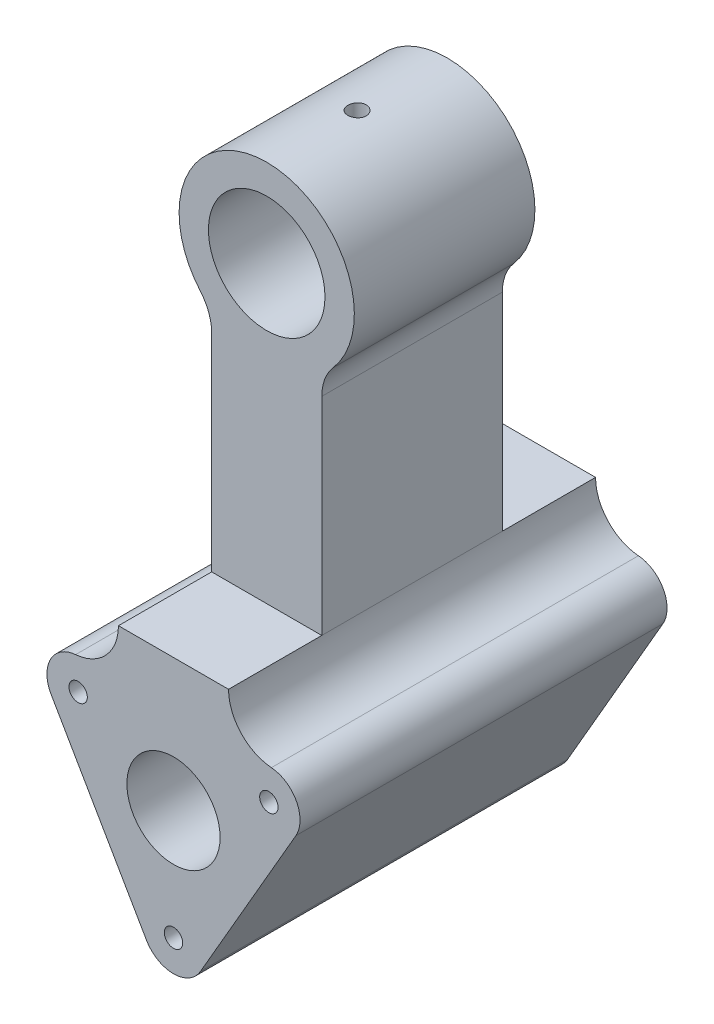
SolidWorks part; units mm, degrees
material "6061-T6 (SS)"
ref_plane "Front Plane" through (0, 0, 0) normal (0, 0, 1) x (1, 0, 0)
ref_plane "Top Plane" through (0, 0, 0) normal (0, 1, 0) x (1, 0, 0)
ref_plane "Right Plane" through (0, 0, 0) normal (1, 0, 0) x (0, 0, -1)
sketch "Sketch1" plane through (0, 0, 0) normal (0, 0, 1) x (1, 0, 0)
  line L22 (-16.671, -52.8382) -> (-3.6806, -75.3382)
  line L23 (3.6806, -75.3382) -> (16.671, -52.8382)
  line L24 (-7.5, -11.9419) -> (-7.5, -40.1481)
  line L25 (7.5, -11.9419) -> (7.5, -40.1481)
  line L26 (-7.5, -40.1481) -> (7.5, -40.1481)
  line L27 (-12.9904, -50.7132) -> (0, -58.2132) construction
  line L28 (0, -58.2132) -> (12.9904, -50.7132) construction
  line L29 (0, -73.2132) -> (0, -58.2132) construction
  circle A0 centre (0, 0) radius 7.9375
  arc A26 (-9.0408, -7.7953) -> (9.0408, -7.7953) centre (0, 0) cw
  arc A30 (-13.335, -46.4772) -> (-16.671, -52.8382) centre (-12.9904, -50.7132) ccw
  arc A31 (-3.6806, -75.3382) -> (3.6806, -75.3382) centre (0, -73.2132) ccw
  arc A32 (16.671, -52.8382) -> (13.335, -46.4772) centre (12.9904, -50.7132) ccw
  circle A33 centre (0, -73.2132) radius 1.65 construction
  circle A34 centre (12.9904, -50.7132) radius 1.65 construction
  circle A35 centre (-12.9904, -50.7132) radius 1.25
  circle A36 centre (12.9904, -50.7132) radius 1.25
  circle A37 centre (0, -73.2132) radius 1.25
  arc A38 (-7.5, -40.1481) -> (-13.335, -46.4772) centre (-13.85, -40.1481) cw
  arc A39 (7.5, -40.1481) -> (13.335, -46.4772) centre (13.85, -40.1481) ccw
  arc A40 (9.0408, -7.7953) -> (7.5, -11.9419) centre (13.85, -11.9419) ccw
  arc A41 (-9.0408, -7.7953) -> (-7.5, -11.9419) centre (-13.85, -11.9419) cw
  circle A42 centre (0, -58.2132) radius 6.35
  point P32 (7.5, -9.2873)
  point P35 (-7.5, -9.2873)
  dimension "D1" = 15.875
  dimension "D2" = 2.5
  dimension "D4" = 4
  dimension "D8" = 12.7
  dimension "D3" = 3
  dimension "D5" = 6.35
  dimension "D7" = 6.35
  dimension "D6" = 15
extrude "Boss-Extrude1" add sketch "Sketch1" along normal mid plane 50 contours A39 L26 A38 A30 L22 A31 L23 A32 A37 A36 A35 region at (-16.3042, -48.9753, 0)
extrude "Boss-Extrude2" add sketch "Sketch1<3>" along normal mid plane 24.6 contours A0 region at (0, -16.2654, 0)
sketch "Sketch1<3>" plane through (0, 0, 0) normal (0, 0, 1) x (1, 0, 0) same geometry as "Sketch1"
sketch "Sketch3" plane through (0, 0, 0) normal (0, 1, 0) x (1, 0, 0)
  circle A0 centre (0, 0) radius 1.25
  dimension "D1" = 2.5
extrude "Cut-Extrude1" cut sketch "Sketch3" along normal through all
